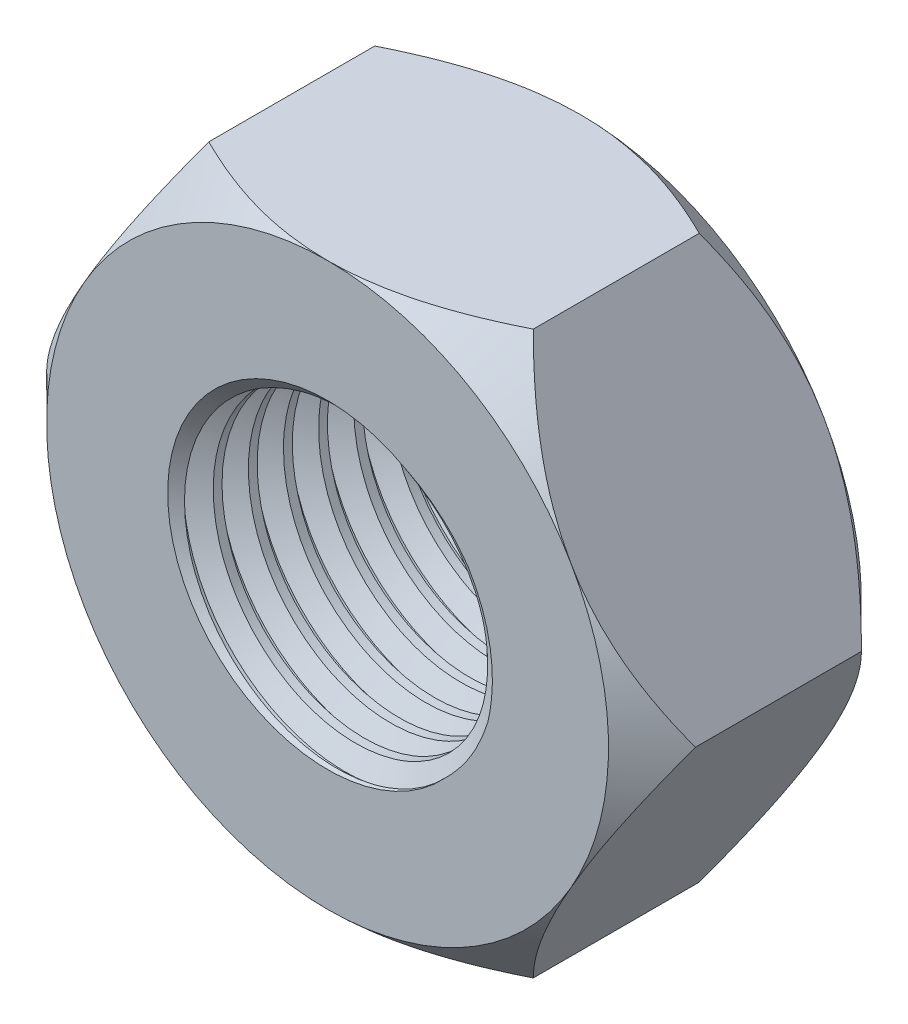
SolidWorks part; units mm, degrees
ref_plane "Front Plane" through (0, 0, 0) normal (0, 0, 1) x (1, 0, 0)
ref_plane "Top Plane" through (0, 0, 0) normal (0, 1, 0) x (1, 0, 0)
ref_plane "Right Plane" through (0, 0, 0) normal (1, 0, 0) x (0, 0, -1)
sketch "Sketch1" plane through (0, 0, 0) normal (0, 0, 1) x (1, 0, 0)
  line L1 (5.7735, 10) -> (-5.7735, 10)
  line L2 (-5.7735, 10) -> (-11.547, 0)
  line L3 (-11.547, 0) -> (-5.7735, -10)
  line L4 (-5.7735, -10) -> (5.7735, -10)
  line L5 (5.7735, -10) -> (11.547, 0)
  line L6 (11.547, 0) -> (5.7735, 10)
  circle A0 centre (0, 0) radius 10 construction
  dimension "D1" = 20
extrude "Boss-Extrude1" add sketch "Sketch1" along normal mid plane 9
sketch "Sketch2" plane through (0, 0, 4.5) normal (0, 0, 1) x (1, 0, 0)
  line L0 (5.7735, 10) -> (-5.7735, 10) construction
  circle A0 centre (0, 0) radius 10
extrude "Cut-Extrude1" cut sketch "Sketch2" against normal through all draft 45 flip side to cut
mirror "Mirror1" about plane through (0, 0, 0) normal (0, 0, 1) of "Cut-Extrude1"
sketch "Sketch3" plane through (0, 0, 4.5) normal (0, 0, 1) x (1, 0, 0)
  circle A0 centre (0, 0) radius 5.19
  dimension "D1" = 10.38
extrude "Cut-Extrude2" cut sketch "Sketch3" against normal through all
chamfer "Chamfer1" distance 0.5 angle 45 2 edges at (5.19, 0, -4.5) (5.19, 0, 4.5)
thread "Thread1" pitch 1.25 method cut profile "Thread Profile2" start angle 0, offset 2, length 0, pitch 1.25, diameter 10.38
ref_plane "Plane2" through (5.19, 0, -6) normal (0, -1, 0) x (1, 0, 0)
sketch "Thread Profile2" plane through (5.19, 0, -6) normal (0, -1, 0) x (1, 0, 0)
  line L0 (0, 0) -> (0, 1.25) construction
  line L1 (0, 0) -> (0.6766, 0.3906)
  line L2 (0.6766, 0.3906) -> (0.6766, 0.5469)
  line L3 (0.6766, 0.5469) -> (0, 0.9375)
  line L4 (0.6766, 0.4687) -> (0, 0.4687) construction
  line L11 (0, 0) -> (0, 0.9375)
  point P2 (0, 0)
  dimension "Pitch" = 1.25
  dimension "Profile_Angle" = 60
  dimension "Profile_Land" = 0.1562
  dimension "Profile_Height" = 0.6766
